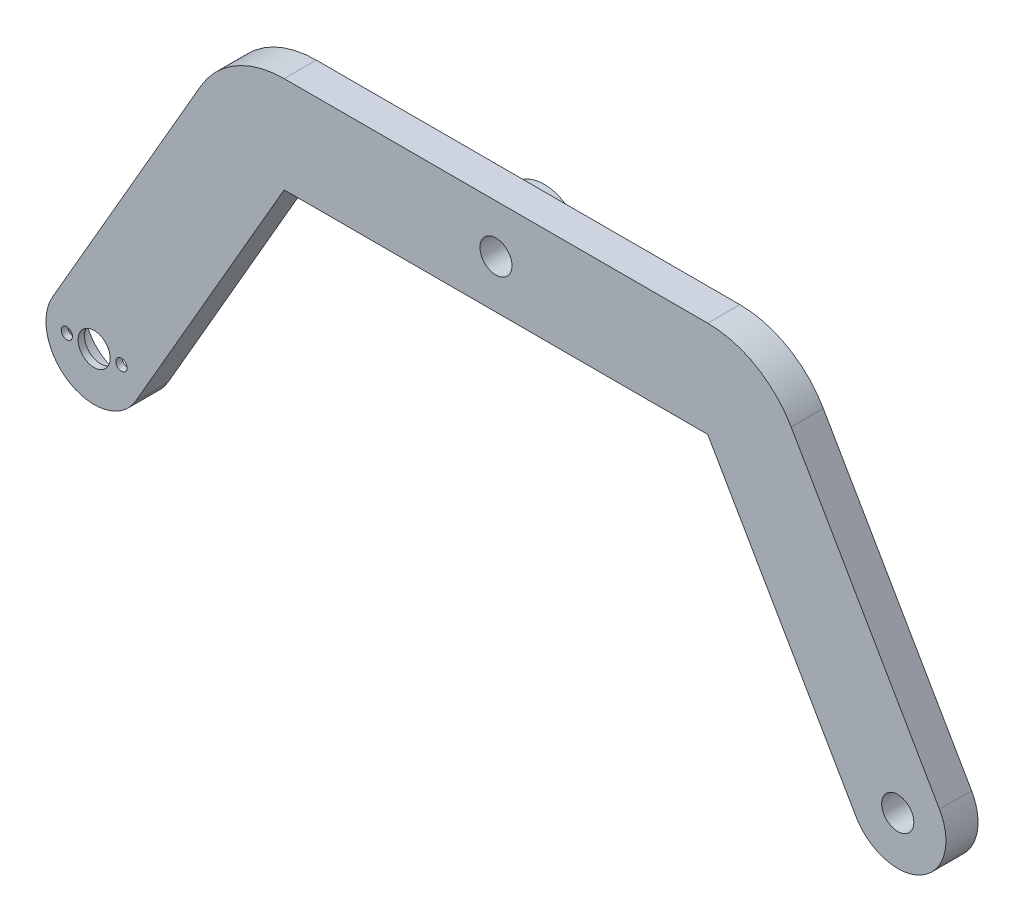
SolidWorks part; units mm, degrees
ref_plane "Front Plane" through (0, 0, 0) normal (0, 0, 1) x (1, 0, 0)
ref_plane "Top Plane" through (0, 0, 0) normal (0, 1, 0) x (1, 0, 0)
ref_plane "Right Plane" through (0, 0, 0) normal (1, 0, 0) x (0, 0, -1)
sketch "Sketch1" plane through (0, 0, 0) normal (0, 0, 1) x (1, 0, 0)
  line L0 (0, -15) -> (0, 15) construction
  line L1 (65.9559, 15) -> (-65.9559, 15)
  line L2 (65.9559, -15) -> (-65.9559, -15)
  line L3 (-65.9559, -15) -> (-112.1545, -95.0183)
  line L5 (-138.1353, -80.0183) -> (-91.9367, 0)
  line L6 (138.1353, -80.0183) -> (91.9367, 0)
  line L8 (65.9559, -15) -> (112.1545, -95.0183)
  arc A1 (-91.9367, 0) -> (-65.9559, 15) centre (-65.9559, -15) cw
  arc A2 (91.9367, 0) -> (65.9559, 15) centre (65.9559, -15) ccw
  circle A3 centre (-125.1449, -87.5183) radius 15 construction
  arc A5 (-138.1353, -80.0183) -> (-112.1545, -95.0183) centre (-125.1449, -87.5183) ccw
  arc A6 (112.1545, -95.0183) -> (138.1353, -80.0183) centre (125.1449, -87.5183) ccw
  circle A7 centre (-133.6449, -87.5183) radius 1.75
  circle A8 centre (-116.6449, -87.5183) radius 1.75
  point P4 (0, 0)
  point P6 (0, 15)
  point P10 (0, -15)
  dimension "D2" = 3.5
  dimension "D4" = 3.5
  dimension "D1" = 30
  dimension "D3" = 120
extrude "Boss-Extrude1" add sketch "Sketch1" along normal blind 10
sketch "Sketch2" plane through (0, 0, 10) normal (0, 0, 1) x (1, 0, 0)
  circle A0 centre (0, 0) radius 5
  circle A1 centre (-125.1449, -87.5183) radius 5
  circle A2 centre (125.1449, -87.5183) radius 5
extrude "Cut-Extrude1" cut sketch "Sketch2" against normal up to surface (10 mm away) up to face at (-131.8949, -87.5183, 0)
sketch "Sketch3" plane through (0, 0, 0) normal (0, 0, -1) x (-1, 0, 0)
  circle A0 centre (0, 0) radius 12
extrude "Boss-Extrude2" add sketch "Sketch3" along normal blind 5
sketch "Sketch4" plane through (0, 0, 0) normal (0, 0, -1) x (-1, 0, 0)
  circle A0 centre (125.1449, -87.5183) radius 13
  dimension "D1" = 26
extrude "Cut-Extrude2" cut sketch "Sketch4" against normal offset from surface (8 mm away) 2 up to face at (5, 0, 10)
